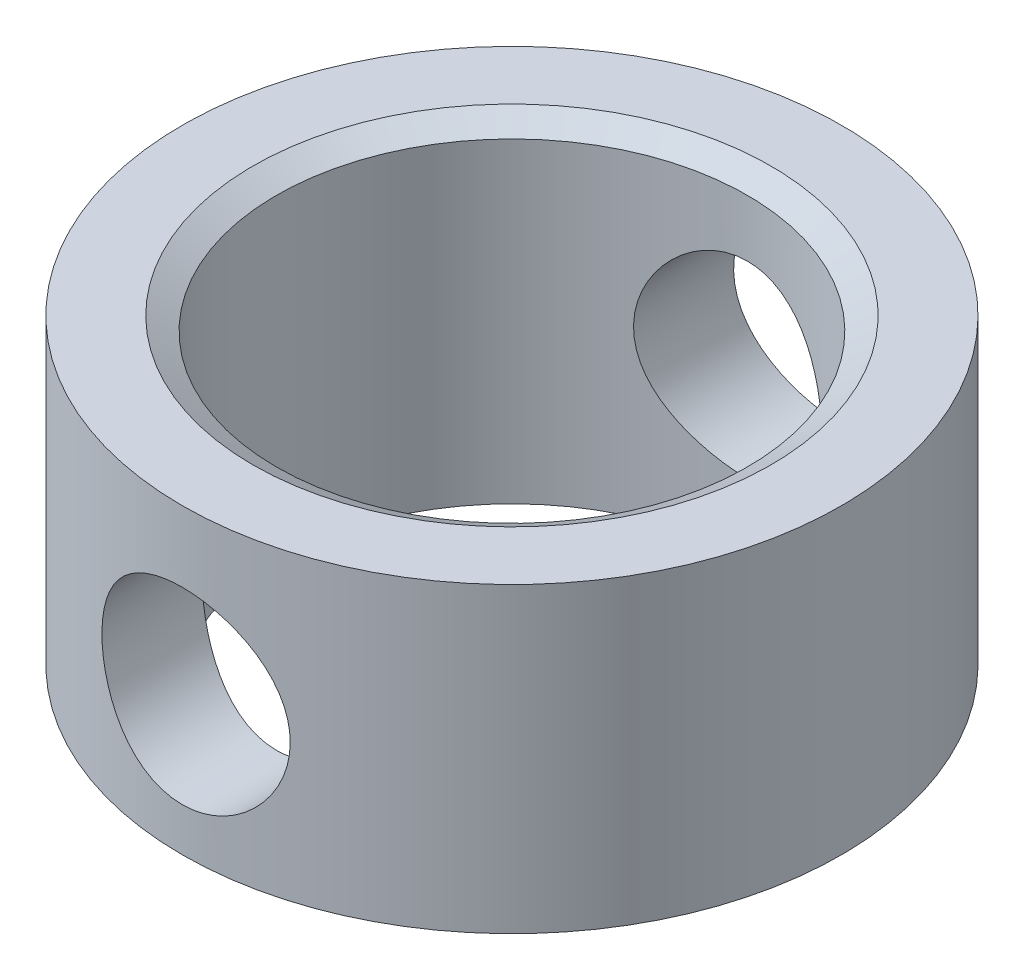
SolidWorks part; units mm, degrees
ref_plane "Front Plane" through (0, 0, 0) normal (0, 0, 1) x (1, 0, 0)
ref_plane "Top Plane" through (0, 0, 0) normal (0, 1, 0) x (1, 0, 0)
ref_plane "Right Plane" through (0, 0, 0) normal (1, 0, 0) x (0, 0, -1)
sketch "Sketch1" plane through (0, 0, 0) normal (0, 1, 0) x (1, 0, 0)
  circle A0 centre (0, 0) radius 5
  circle A1 centre (0, 0) radius 7
  dimension "D1" = 10
  dimension "D2" = 2
extrude "Boss-Extrude1" add sketch "Sketch1" along normal blind 7
chamfer "Chamfer1" distance 0.5 angle 30 1 edges at (0, 7, 5) first distance on face at (0, 7, 7)
chamfer "Chamfer2" distance 1 angle 30 1 edges at (0, 0, 7) first distance on face at (0, 0, 7)
sketch "Sketch2" plane through (0, 0, 0) normal (0, 0, 1) x (1, 0, 0)
  line L1 (7, 7) -> (-7, 7) construction
  circle A0 centre (0, 3.5) radius 2
  point P2 (0, -1)
  dimension "D1" = 4
  dimension "D2" = 3.5
extrude "Cut-Extrude1" cut sketch "Sketch2" against normal through all both and the other way through all
